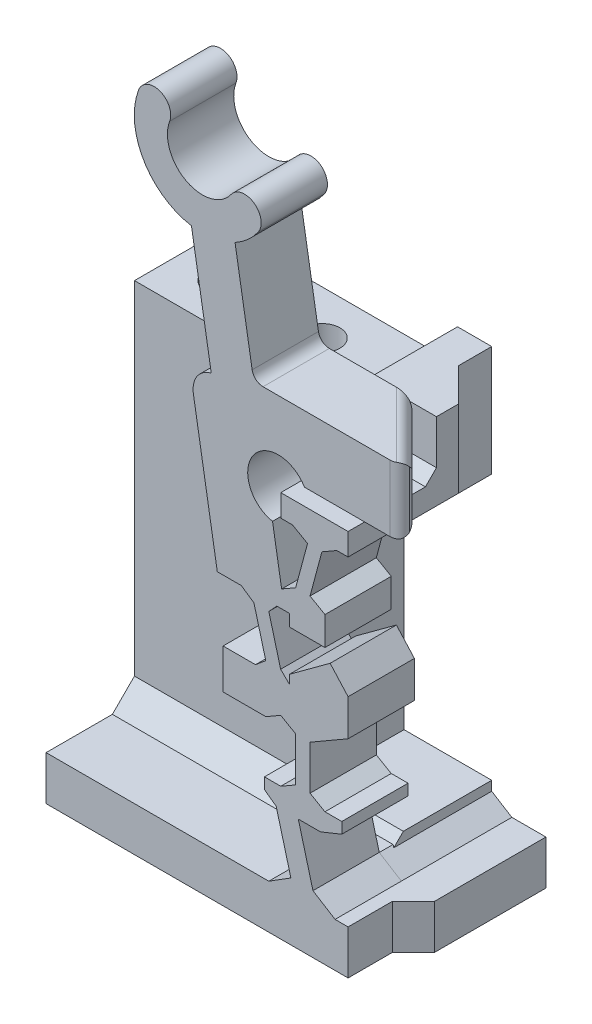
SolidWorks part; units mm, degrees
material "Nylon 6/12"
ref_plane "Front Plane" through (0, 0, 0) normal (0, 0, 1) x (1, 0, 0)
ref_plane "Top Plane" through (0, 0, 0) normal (0, 1, 0) x (1, 0, 0)
ref_plane "Right Plane" through (0, 0, 0) normal (1, 0, 0) x (0, 0, -1)
sketch "Sketch-SkeletonConfigUp" plane through (0, 0, 0) normal (0, 0, 1) x (1, 0, 0)
  line L0 (0, 0) -> (0, -50000) construction
  line L1 (0, 0) -> (4.5811, 6.2164) construction
  line L2 (9.8143, 13.3177) -> (4.5811, 13.945) construction
  line L3 (4.5811, 13.945) -> (2.9713, 10.4094) construction
  line L4 (2.9713, 10.4094) -> (4.5811, 6.2164) construction
  line L5 (4.5811, 13.945) -> (6.2429, 19.1409) construction
  line L6 (2.9713, 10.4094) -> (0.0405, 27.8193) construction
  line L7 (4.5811, 6.2164) -> (9.8143, 13.3177) construction
  line L8 (-587.3593, -797.0242) -> (9.8143, 13.3177) construction
  point P12 (0, 0)
  point P13 (0, 0)
  dimension "D2" = 7.7221
  dimension "D3" = 8.8212
  dimension "D4" = 5.2707
  dimension "D5" = 119.553
  dimension "D6" = 3.8848
  dimension "D7" = 5.4552
  dimension "D8" = 17.6549
  dimension "D9" = 4.4914
  dimension "D10" = 6.745
  dimension "D11" = 145.964
  dimension "D12" = 143.612
sketch "Sketch-SkeletonConfigDown" plane through (0, 0, 0) normal (0, 0, 1) x (1, 0, 0)
  line L0 (0, 0) -> (0, -50000) construction
  line L1 (0, 0) -> (4.5811, 6.2164) construction
  line L2 (9.8143, 13.3177) -> (4.5811, 13.945) construction
  line L3 (4.5811, 13.945) -> (6.1909, 10.4094) construction
  line L4 (6.1909, 10.4094) -> (4.5811, 6.2164) construction
  line L5 (4.5811, 13.945) -> (1.753, 18.6098) construction
  line L6 (6.1909, 10.4094) -> (-8.8652, 19.6294) construction
  line L7 (4.5811, 6.2164) -> (9.8143, 13.3177) construction
  line L8 (-589.9357, -800.5203) -> (9.8143, 13.3177) construction
  dimension "D2" = 7.7221
  dimension "D3" = 8.8212
  dimension "D4" = 5.2707
  dimension "D5" = 119.553
  dimension "D6" = 3.8848
  dimension "D7" = 5.4552
  dimension "D8" = 17.6549
  dimension "D9" = 4.4914
  dimension "D10" = 6.745
  dimension "D11" = 145.964
  dimension "D1" = 143.612
ref_plane "Plane-Cam Base" through (9.128, 0, 0) normal (1, 0, 0) x (0, 0, -1)
ref_plane "Plane-Down-to-Up Derailleur Clearance" through (6.628, 0, 0) normal (1, 0, 0) x (0, 0, -1)
ref_plane "Plane-Cam Cavity Roof" through (5.128, 0, 0) normal (1, 0, 0) x (0, 0, -1)
sketch "Sketch-SwitchBossUp" plane through (0, 0, 0) normal (0, 0, 1) x (1, 0, 0)
  line L0 (3.5811, 11.4759) -> (3.5811, 12.945) construction
  line L5 (5.5811, 12.5552) -> (5.5811, 11.263)
  line L7 (1.5115, 25.1048) -> (2.3566, 20.0847)
  line L8 (-0.4607, 24.7728) -> (0.4359, 19.4465)
  line L9 (2.9713, 10.4094) -> (0.0405, 27.8193) construction
  line L11 (-0.0396, 22.2712) -> (1.9326, 22.6032) construction
  line L15 (6.628, -23.7286) -> (6.628, 23.7286) construction
  line L16 (2.9713, 10.4094) -> (4.5811, 6.2164) construction
  line L17 (3.5811, 12.945) -> (3.5811, 14.945) construction
  line L18 (5.5811, 12.945) -> (5.5811, 14.945) construction
  line L19 (4.2561, 13.945) -> (4.9061, 13.945) construction
  line L20 (3.5811, 14.945) -> (5.5811, 14.945) construction
  line L21 (3.5811, 12.945) -> (5.5811, 12.945) construction
  line L22 (4.5811, 12.945) -> (4.5811, 14.945) construction
  line L23 (4.5811, 6.2164) -> (8.5405, 7.1023) construction
  line L24 (1.9713, 9.4094) -> (1.9713, 11.4094) construction
  line L25 (3.9713, 9.4094) -> (3.9713, 11.4094) construction
  line L26 (3.9713, 9.4094) -> (1.9713, 9.4094) construction
  line L27 (1.9713, 11.4094) -> (3.9713, 11.4094) construction
  line L28 (3.5811, 7.2164) -> (5.5811, 7.2164) construction
  line L29 (3.5811, 7.2164) -> (3.5811, 5.2164) construction
  line L30 (5.5811, 7.2164) -> (5.5811, 5.2164) construction
  line L31 (3.5811, 5.2164) -> (5.5811, 5.2164) construction
  line L32 (4.9061, 6.2164) -> (4.2561, 6.2164) construction
  line L40 (2.6348, 10.4094) -> (3.3077, 10.4094) construction
  line L66 (0.0405, 27.8193) -> (0.0405, 50027.8193) construction
  line L74 (0.7092, 11.7991) -> (-0.3728, 18.2264)
  line L75 (0.3841, 13.7302) -> (2.3564, 14.0622) construction
  line L76 (5.5811, 11.263) -> (5.5811, 12.5552) construction
  line L77 (5.5811, 7.6061) -> (6.628, 8.2105)
  line L80 (5.8152, 10.763) -> (6.628, 9.8603)
  line L81 (9.128, 1033.2419) -> (9.128, 20.0586) construction
  line L82 (4.6532, 17.0847) -> (9.028, 17.0847)
  line L85 (6.9307, 9.5241) -> (8.5405, 7.7363) construction
  line L88 (5.7256, 16.3347) -> (6.628, 16.3347)
  line L92 (3.7762, 8.3129) -> (6.9307, 9.5241) construction
  line L95 (2.3566, 20.0847) -> (7.4359, 20.0847)
  line L96 (7.4359, 20.0847) -> (9.028, 20.0847)
  line L97 (3.2085, 15.0241) -> (3.6203, 12.5779)
  line L98 (1.9713, 9.0197) -> (0.9713, 9.0197)
  line L99 (0.9713, 9.0197) -> (0.9713, 7.2164)
  line L100 (0.9713, 7.2164) -> (2.9061, 7.2164)
  line L101 (4.5811, 6.2164) -> (6.9307, 9.5241) construction
  line L103 (0.0405, 27.8193) -> (1.9448, 26.4638) construction
  line L104 (6.9307, 9.5241) -> (8.5405, 7.7363) construction
  line L107 (1.9713, 9.4094) -> (1.9713, 9.0197) construction
  line L109 (0.0405, 27.8193) -> (-2.1498, 28.6358) construction
  line L111 (6.628, 9.8603) -> (6.628, 8.2105)
  line L112 (6.628, 9.8603) -> (6.9307, 9.5241) construction
  line L113 (2.8424, 4.8267) -> (2.8424, 4.3267)
  line L114 (7.3693, 7.7363) -> (7.3563, 7.7363) construction
  line L121 (5.0383, -1.1653) -> (5.0383, 1.4614) construction
  line L122 (2.8616, 17.0847) -> (3.2085, 15.0241) construction
  line L127 (5.5811, 15.3347) -> (5.5811, 14.945) construction
  line L130 (6.0388, 0.837) -> (6.628, 0.837)
  line L132 (2.8424, 4.3267) -> (3.3749, 3.937)
  line L133 (2.9028, 9.4094) -> (2.4375, 9.0197)
  line L134 (4.5811, 10.4094) -> (4.5811, 13.945) construction
  line L135 (4.5811, 10.4094) -> (4.5811, 6.2164) construction
  line L137 (3.9713, 9.4094) -> (5.5811, 7.2164) construction
  line L139 (5.8152, 10.763) -> (3.9713, 9.4094)
  line L141 (4.0386, 1.4604) -> (3.0388, 0.8347)
  line L142 (3.0388, 0.8347) -> (3.0388, -1.1653)
  line L143 (9.128, 20.0586) -> (9.128, 18.3333) construction
  line L145 (9.128, 16.6071) -> (9.128, -49992.4167) construction
  line L147 (5.5811, 11.263) -> (5.5811, 12.5552) construction
  line L150 (3.0388, -1.1653) -> (5.0383, -1.1653)
  line L151 (3.3749, 3.937) -> (4.3749, 3.937) construction
  line L152 (4.792, 14.945) -> (4.2561, 12.945)
  line L153 (5.442, 14.945) -> (4.9061, 12.945)
  line L157 (3.5811, 16.3347) -> (3.5811, 15.3347)
  line L158 (6.117, 15.3347) -> (6.628, 15.3347)
  line L162 (3.0398, 11.4094) -> (3.5757, 9.4094)
  line L164 (2.3668, 11.4094) -> (2.9028, 9.4094)
  line L169 (4.2561, 7.2164) -> (4.2561, 5.2164)
  line L170 (4.9061, 5.2164) -> (4.9061, 7.2164)
  line L175 (4.2561, 7.2164) -> (3.5811, 7.6061)
  line L176 (4.9061, 7.2164) -> (5.5811, 7.6061)
  line L177 (5.5811, 7.2164) -> (5.5811, 7.6061) construction
  line L179 (4.2561, 5.2164) -> (3.5811, 4.8267)
  line L180 (3.5811, 5.2164) -> (3.5811, 4.8267) construction
  line L181 (3.5811, 4.8267) -> (2.8424, 4.8267)
  line L183 (4.9061, 5.2164) -> (5.5811, 4.8267)
  line L184 (5.5811, 5.2164) -> (5.5811, 4.8267) construction
  line L186 (9.128, -23.7286) -> (9.128, 23.7286) construction
  line L191 (3.9713, 11.4094) -> (3.9713, 11.7991) construction
  line L192 (3.9713, 11.7991) -> (3.9713, 11.263)
  line L193 (4.9061, 12.945) -> (5.5811, 12.5552)
  line L194 (4.2561, 12.945) -> (3.6203, 12.5779)
  line L195 (3.9713, 11.263) -> (5.5811, 11.263)
  line L196 (3.9713, 9.4094) -> (3.9713, 9.0197)
  line L197 (3.5811, 7.2164) -> (3.5811, 7.6061) construction
  line L199 (3.5811, 7.6061) -> (2.9061, 7.2164)
  line L201 (2.8424, 4.3267) -> (2.8424, 3.937) construction
  line L202 (2.8424, 3.937) -> (3.3749, 3.937) construction
  line L204 (5.0383, 1.437) -> (3.0388, 1.437) construction
  line L205 (3.0388, 1.437) -> (3.0388, 0.8347) construction
  line L206 (5.0383, 1.4614) -> (6.0388, 0.837)
  line L207 (9.128, 18.3333) -> (9.128, 16.6071) construction
  line L208 (6.628, -1.1653) -> (6.628, 0.837)
  line L209 (9.128, 20.0586) -> (9.128, 16.6071) construction
  line L211 (5.0383, 1.4614) -> (4.3749, 3.937)
  line L212 (4.0386, 1.4604) -> (3.3749, 3.937)
  line L214 (4.792, 14.945) -> (4.1169, 15.3347)
  line L215 (4.1169, 15.3347) -> (3.5811, 15.3347)
  line L216 (5.442, 14.945) -> (6.117, 15.3347)
  line L217 (5.5811, 12.945) -> (5.5811, 12.5552) construction
  line L218 (5.442, 14.945) -> (5.442, 15.3347) construction
  line L219 (6.117, 15.3347) -> (4.1169, 15.3347) construction
  line L221 (9.028, 17.0847) -> (9.028, 20.0847)
  line L224 (3.5811, 16.3347) -> (5.7256, 16.3347)
  line L232 (6.628, 15.3347) -> (6.628, 16.3347)
  line L233 (6.628, -1.1653) -> (5.0383, -1.1653)
  line L236 (2.4375, 9.0197) -> (1.9713, 9.0197)
  line L240 (4.3749, 3.937) -> (5.3749, 3.937)
  line L241 (5.3749, 3.937) -> (6.3424, 4.3267)
  line L248 (2.8616, 17.0847) -> (4.6532, 17.0847) construction
  line L249 (3.5757, 9.4094) -> (3.9713, 9.0197)
  line L250 (3.0398, 11.4094) -> (3.4039, 11.7991)
  line L251 (3.4039, 11.7991) -> (3.9713, 11.7991)
  line L252 (2.3668, 11.4094) -> (1.794, 11.7991)
  line L253 (1.794, 11.7991) -> (0.7092, 11.7991)
  line L254 (1.794, 11.7991) -> (3.4039, 11.7991) construction
  line L256 (2.4375, 9.0197) -> (3.9713, 9.0197) construction
  line L367 (5.5811, 4.8267) -> (6.3424, 4.8267)
  line L368 (6.3424, 4.8267) -> (6.3424, 4.3267)
  arc A0 (1.5115, 25.1048) -> (2.5558, 26.0289) centre (0.0405, 27.8193) ccw
  arc A1 (-0.4607, 24.7728) -> (-2.8525, 28.8978) centre (0.0405, 27.8193) cw
  arc A2 (-2.8525, 28.8978) -> (-1.447, 28.3738) centre (-2.1498, 28.6358) cw
  arc A3 (2.5558, 26.0289) -> (1.3338, 26.8987) centre (1.9448, 26.4638) ccw
  arc A4 (-1.447, 28.3738) -> (1.3338, 26.8987) centre (0.0405, 27.8193) ccw
  arc A5 (3.5811, 12.945) -> (3.5811, 14.945) centre (3.1778, 13.945) ccw construction
  arc A6 (5.5811, 12.945) -> (5.5811, 14.945) centre (5.9843, 13.945) cw construction
  arc A9 (3.5811, 7.2164) -> (3.5811, 5.2164) centre (3.1779, 6.2164) cw construction
  arc A10 (5.5811, 7.2164) -> (5.5811, 5.2164) centre (5.9844, 6.2164) ccw construction
  arc A19 (-0.3728, 18.2264) -> (0.4359, 19.4465) centre (0.6836, 18.4042) cw
  circle A28 centre (0.0405, 27.8193) radius 2.3375 construction
  arc A37 (3.2085, 15.0241) -> (4.6532, 17.0847) centre (3.4651, 16.381) cw
  point P53 (4.5811, 13.945)
  point P93 (0.9465, 22.4372)
  dimension "D23" = 1.5875
  dimension "D24" = 0.75
  dimension "D2" = 2
  dimension "D5" = 2
  dimension "D6" = 0.65
  dimension "D8" = 42
  dimension "D16" = 42
  dimension "D27" = 120
  dimension "D28" = 120
  dimension "D29" = 120
  dimension "D30" = 120
  dimension "D17" = 0.5
  dimension "D21" = 1
  dimension "D9" = 17.5
  dimension "D22" = 1
  dimension "D38" = 2
  dimension "D39" = 0.5
  dimension "D40" = 60
  dimension "D41" = 1
  dimension "D42" = 45
  dimension "D43" = 120
  dimension "D10" = 15
  dimension "D12" = 2.5
  dimension "D13" = 1
  dimension "D19" = 1
  dimension "D25" = 15
  dimension "D26" = 120
  dimension "D35" = 120
  dimension "D20" = 3
  dimension "D48" = 2
  dimension "D49" = 0.6
  dimension "D7" = 0.75
  dimension "D14" = 3
  dimension "D82" = 1
  dimension "D83" = 3.5
  dimension "D15" = 0.65
  dimension "D18" = 15
extrude "Boss-Switch Body" add sketch "Sketch-SwitchBossUp" along normal blind 3
sketch "Sketch1" plane through (0, 0, 0) normal (0, 0, -1) x (-1, 0, 0)
  line L1 (-7.5811, -1.1653) -> (0.4122, -1.1653)
  line L2 (-7.5811, -1.1653) -> (-7.5811, 0.837)
  line L4 (0.4122, -1.1653) -> (0.4122, 0.8347)
  line L5 (-3.5811, 18.8347) -> (-7.5811, 18.8347)
  line L10 (-7.5811, 18.8347) -> (-7.5811, 15.3347)
  line L11 (-4.0386, 1.4604) -> (-5.0386, 1.4604)
  line L12 (-7.5811, 15.3347) -> (-3.5811, 15.3347)
  line L13 (-4.0386, 1.4604) -> (-3.0388, 0.8347)
  line L14 (-3.5811, 15.3347) -> (-3.5811, 18.8347)
  line L20 (-4.3749, 3.937) -> (-5.0383, 1.4614) construction
  line L22 (-3.0388, -1.1653) -> (-6.628, -1.1653) construction
  line L23 (-3.0388, 0.8347) -> (0.4122, 0.8347)
  line L24 (-5.0386, 1.4604) -> (-6.0388, 0.837)
  line L25 (-6.0388, 0.837) -> (-7.5811, 0.837)
  dimension "D1" = 3.5
extrude "Boss-Flange Width" add sketch "Sketch1" along normal blind 5
ref_plane "Plane-Sta2Sit Groove" through (0.0405, 0, 0) normal (1, 0, 0) x (0, 0, -1)
ref_plane "Plane-Cam Outer Surface" through (-12.0395, 0, 0) normal (1, 0, 0) x (0, 0, -1)
ref_plane "Plane-FlangeTop" through (-7.0395, 0, 0) normal (1, 0, 0) x (0, 0, -1)
sketch "Sketch2" plane through (-7.0395, 0, 0) normal (1, 0, 0) x (0, 0, -1)
  line L0 (5, 15.3347) -> (-3, 15.3347) construction
  line L1 (5, 17.3347) -> (1, 17.3347)
  line L2 (5, 17.3347) -> (5, 15.3347)
  line L3 (5, 15.3347) -> (1, 15.3347)
  line L4 (1, 17.3347) -> (1, 15.3347)
  line L5 (-3, -1.1653) -> (-3, 0.837) construction
  line L11 (5, 0.8347) -> (-3, 0.8347)
  line L12 (5, 0.8347) -> (5, -1.1653)
  line L13 (5, -1.1653) -> (-3, -1.1653)
  line L14 (-3, 0.8347) -> (-3, -1.1653)
  line L15 (0, 10.4094) -> (0, 27.8193) construction
  line L17 (5, 0.837) -> (5, -1.1653) construction
  line L18 (-3, 0.8347) -> (0, 0.8347) construction
  dimension "D1" = 1
  dimension "D2" = 2
extrude "Boss-Flange Height" add sketch "Sketch2" along normal up to surface (11.6675 mm away)
sketch "Sketch24" plane through (0, 0, 0) normal (0, 0, 1) x (1, 0, 0)
  line L0 (3.5811, 16.3347) -> (7.5811, 16.3347)
  line L1 (7.5811, 17.0847) -> (7.5811, 15.3347) construction
  line L2 (3.5811, 16.3347) -> (3.5811, 18.8347)
  line L3 (3.5811, 18.8347) -> (7.5811, 18.8347)
  line L4 (7.5811, 18.8347) -> (7.5811, 16.3347)
extrude "Cut-Wall Clearance" cut sketch "Sketch24" against normal up to surface (1 mm away) up to face at (-1.7292, 16.3347, -1)
sketch "Sketch10" plane through (0, 15.3347, 0) normal (0, 1, 0) x (1, 0, 0)
  line L0 (9.128, -23.7286) -> (9.128, 23.7286) construction
  line L1 (7.5811, 5) -> (5.128, 5)
  line L2 (7.5811, 5) -> (7.5811, 2)
  line L3 (7.5811, 2) -> (5.128, 2)
  line L5 (4.628, 7) -> (4.628, 1) construction
  line L6 (3.5811, 1) -> (-7.0395, 1) construction
  line L8 (5.128, 5) -> (5.128, 2)
  dimension "D1" = 1
  dimension "D2" = 0.5
  dimension "D3" = 4.5
extrude "Cut-Up-To-Down Derailleur Clearance" cut sketch "Sketch10" along normal up to next
sketch "Sketch17" plane through (0, 15.3347, 0) normal (0, -1, 0) x (1, 0, 0)
  line L0 (5.128, -5) -> (-7.0395, -5)
  line L1 (5.128, -5) -> (-7.0395, -5) construction
  line L2 (-7.0395, -5) -> (-7.0395, -1)
  line L3 (-7.0395, -1) -> (5.128, -1)
  line L4 (5.128, -1) -> (5.128, -5)
  line L5 (-7.0395, -1) -> (-7.0395, -5) construction
extrude "Boss-Flange Support" add sketch "Sketch17" along normal up to surface (14.5 mm away) up to face at (-2.0003, 0.8347, -1)
sketch "Sketch-HolePositions" plane through (0, -1.1653, 0) normal (0, -1, 0) x (1, 0, 0)
  line L0 (-7.0395, -3) -> (7.5811, -3) construction
  line L1 (7.5811, -5) -> (-7.0395, -5) construction
  line L2 (7.5811, -5) -> (7.5811, 0) construction
  line L4 (-7.0395, -22.2167) -> (-7.0395, 22.2167) construction
  point P6 (-5.0395, -3)
  point P7 (-0.5395, -3)
  dimension "D1" = 2
  dimension "D2" = 4.5
  dimension "D3" = 2
sketch "Sketch6" plane through (0, -1.1653, 0) normal (0, -1, 0) x (-1, 0, 0)
  point P0 (5.0395, 3)
  point P3 (0.5395, 3)
hole_wizard "Tap Drill for M2x0.4 Tap1" positions "Sketch6" profile "Sketch5" hole size "M2x0.4" standard "ANSI Metric" end condition through all
sketch "Sketch5" plane through (-5.0395, -1.1653, -3) normal (1, 0, 0) x (0, 0, -1)
  line L0 (0, 0) -> (0, 30.5511)
  line L1 (0, 30.5511) -> (0.8, 30.5511)
  line L2 (0.8, 30.5511) -> (0.8, 0)
  line L5 (0.8, 0) -> (0, 0)
  line L11 (0, -6.35) -> (0, 107.95) construction
  dimension "Thru Hole Dia." = 1.6
  dimension "Thru Hole Depth" = 30.5511
sketch "Sketch9" plane through (0, -1.1653, 0) normal (0, -1, 0) x (1, 0, 0)
  point P0 (-5.0395, -3)
  point P3 (-0.5395, -3)
hole_wizard "M2 Clearance Hole2" positions "Sketch9" profile "Sketch8" hole size "M2" standard "ANSI Metric"
sketch "Sketch8" plane through (-5.0395, -1.1653, -3) normal (1, 0, 0) x (0, 0, -1)
  line L0 (0, 0) -> (0, 15.721)
  line L1 (0, 15.721) -> (1.2, 15)
  line L2 (1.2, 15) -> (1.2, 0)
  line L5 (1.2, 0) -> (0, 0)
  line L10 (0, 15.721) -> (-1.2, 15) construction
  line L11 (0, -6.35) -> (0, 107.95) construction
  dimension "Hole Dia." = 2.4
  dimension "Hole Depth" = 15
  dimension "Drill Angle" = 118
sketch "Sketch-Measurements for Derailleur Ramps" [suppressed] plane through (0, 0, 0) normal (0, 0, 1) x (1, 0, 0)
  line L0 (3.184, 15.1695) -> (2.4687, 19.4188)
  line L1 (2.8264, 17.2941) -> (1.8402, 17.1281)
  line L2 (2.9713, 10.4094) -> (0.0405, 27.8193) construction
  line L3 (1.8402, 17.1281) -> (-1.3081, 15.0016)
  line L4 (6.1909, 10.4094) -> (-8.8652, 19.6294) construction
  line L5 (1.8402, 17.1281) -> (2.6012, 12.6077)
  line L6 (2.6012, 12.6077) -> (-1.3081, 15.0016)
  line L7 (0.2661, 16.0649) -> (0.2661, 17.1281)
  line L8 (0.2661, 17.1281) -> (1.8402, 17.1281)
  line L9 (6.1909, 10.4094) -> (2.9713, 10.4094)
  line L10 (5.386, 8.3129) -> (3.7762, 8.3129)
  line L11 (2.6116, 18.5698) -> (1.5115, 25.1048) construction
  line L12 (6.1909, 10.4094) -> (4.5811, 6.2164) construction
  line L13 (4.5811, 8.3129) -> (4.5811, 8.7912)
  line L14 (4.5811, 6.2164) -> (5.386, 8.3129)
  line L15 (2.9713, 10.4094) -> (4.5811, 6.2164) construction
  line L16 (3.7762, 8.3129) -> (4.5811, 6.2164)
  line L17 (5.386, 8.3129) -> (5.386, 8.7912)
  dimension "D1" = 1.5742
  dimension "D2" = 0.8049
sketch "Sketch12" plane through (0, 20.0847, 0) normal (0, 1, 0) x (1, 0, 0)
  line L0 (6.528, 0) -> (9.028, -2.5)
  line L1 (9.028, -2.5) -> (9.028, 0)
  line L2 (9.028, 0) -> (6.528, 0)
  line L3 (9.028, -3) -> (9.028, 0) construction
  line L6 (9.028, 0) -> (2.3566, 0) construction
  dimension "D1" = 45
extrude "Cut-Up-to-Down Cantilever Slope" cut sketch "Sketch12" against normal up to next
ref_plane "Plane1" through (0, 7.1023, 0) normal (0, 1, 0) x (1, 0, 0)
ref_plane "Plane-Cantilever Cut" [suppressed] through (7.0848, 8.5204, -1.9058) normal (-0.6301, -0.7578, 0.1695) x (-0.7765, 0.6151, -0.1368)
sketch "Sketch14" [suppressed] plane through (7.0848, 8.5204, -1.9058) normal (-0.6301, -0.7578, 0.1695) x (-0.7765, 0.6151, -0.1368)
  line L0 (2.3023, -1.6911) -> (-0.3551, -1.6911)
  line L2 (2.3023, -4.3362) -> (2.3023, -1.6911)
  line L3 (-0.3551, -1.6911) -> (-0.3551, -4.4608)
  line L5 (-0.3551, -4.4608) -> (1.0087, -5.0843)
  line L6 (1.0087, -5.0843) -> (2.3023, -4.3362)
extrude "Cut-Down-to-Up Cantilever Slope" [suppressed] cut sketch "Sketch14" against normal up to next
ref_plane "Plane-Symmetry Plane" through (0, 0, 1.5) normal (0, 0, 1) x (1, 0, 0)
sketch "Sketch-Cable Center Point" plane through (0, 0, 1.5) normal (0, 0, 1) x (1, 0, 0)
  line L0 (0.0405, 27.8193) -> (0.1722, 27.0366)
  line L1 (2.9713, 10.4094) -> (0.0405, 27.8193) construction
  point P0 (0.0405, 27.8193)
  dimension "D1" = 0.7937
chamfer "Chamfer-Flange Support" distance 1.5 angle 45 1 edges at (3.5811, 17.3347, -3)
chamfer "Chamfer-Flange Support 2" distance 1.5 angle 45 2 edges at (5.128, 17.0847, -2) (5.128, 15.3347, -1.5)
chamfer "Chamfer-Flange Support 3" distance 1 angle 45 1 edges at (-2.0003, 0.8347, -1)
chamfer "Chamfer3" distance 0.5 angle 45 3 edges at (3.5811, 15.8347, -1) (5.1045, 15.3347, -1) (5.5811, 16.3347, -1)
chamfer "Chamfer7" [suppressed] distance 1 angle 45
sketch "Sketch23" plane through (0, 0, -1) normal (0, 0, 1) x (1, 0, 0)
  line L0 (5.128, 1.8347) -> (1.1605, 1.8347)
  line L1 (-7.0395, 1.8347) -> (5.128, 1.8347) construction
  line L2 (1.1605, 1.8347) -> (1.1605, 13.8347)
  line L3 (1.1605, 13.8347) -> (5.128, 13.8347)
  line L4 (5.128, 13.8347) -> (5.128, 1.8347)
  line L5 (0.6605, -1.1653) -> (0.6605, 13.8347) construction
  dimension "D1" = 0.5
extrude "Cut-Gap for Printing" cut sketch "Sketch23" against normal through all
sketch "Sketch25" plane through (0, 0, 0) normal (0, 0, 1) x (1, 0, 0)
  line L0 (6.628, 15.3347) -> (7.5811, 15.3347)
  line L1 (7.5811, 15.3347) -> (7.5811, 18.8347)
  line L2 (7.5811, 18.8347) -> (6.628, 18.8347)
  line L3 (6.628, -23.7286) -> (6.628, 23.7286) construction
  line L4 (7.5811, 18.8347) -> (3.5811, 18.8347) construction
  line L5 (6.628, 18.8347) -> (6.628, 15.3347)
extrude "Cut-Derailleur Clearance" cut sketch "Sketch25" against normal through all
chamfer "Chamfer8" distance 1 angle 45 1 edges at (6.628, -0.1641, 0)
fillet "Fillet1" radius 0.5 5 edges at (6.528, 18.5847, 0) (9.028, 18.5847, 3) (7.778, 20.0847, 1.25) (9.028, 18.5847, 2.5) (7.778, 17.0847, 1.25)
fillet "Fillet2" radius 0.5 1 edges at (2.3566, 20.0847, 1.5)
equation "\"axle-diameter\"=2"
equation "\"switch-thickness\"=12"
equation "\"base-width\"=4.0"
equation "\"axle-bushing-radius\"=3"
equation "\"clearance\"= 0.25"
equation "\"arm-width\"=1.5"
equation "\"min-diameter\"=70"
equation "\"alpha\"=143.6120"
equation "\"gamma\"=119.5526"
equation "\"delta\"=145.9637"
equation "\"epsilon\"=6.7452"
equation "\"l_AB\"=8.8212"
equation "\"l_AC\"=4.4914"
equation "\"l_BD\"=5.2707"
equation "\"l_CD\"=3.8848"
equation "\"l_CE\"=17.6549"
equation "\"l_DF\"=5.4552"
equation "\"l_OA\"=7.7221"
equation "\"D2@Sketch-SkeletonConfigUp\" = \"l_OA\""
equation "\"D3@Sketch-SkeletonConfigUp\" = \"l_AB\""
equation "\"D4@Sketch-SkeletonConfigUp\" = \"l_BD\""
equation "\"D5@Sketch-SkeletonConfigUp\" = \"gamma\""
equation "\"D6@Sketch-SkeletonConfigUp\" = \"l_CD\""
equation "\"D7@Sketch-SkeletonConfigUp\" = \"l_DF\""
equation "\"D8@Sketch-SkeletonConfigUp\" = \"l_CE\""
equation "\"D9@Sketch-SkeletonConfigUp\" = \"l_AC\""
equation "\"D_groove\"=3.175"
equation "\"D7@Sketch-SkeletonConfigDown\" = \"l_DF\""
equation "\"D6@Sketch-SkeletonConfigDown\" = \"l_CD\""
equation "\"D2@Sketch-SkeletonConfigDown\" = \"l_OA\""
equation "\"D3@Sketch-SkeletonConfigDown\" = \"l_AB\""
equation "\"D9@Sketch-SkeletonConfigDown\" = \"l_AC\""
equation "\"D8@Sketch-SkeletonConfigDown\" = \"l_CE\""
equation "\"D5@Sketch-SkeletonConfigDown\" = \"gamma\""
equation "\"D4@Sketch-SkeletonConfigDown\" = \"l_BD\""
equation "\"D1@Sketch-SkeletonConfigDown\" = \"alpha\""
equation "\"hinge_length\"=1.5"
equation "\"hinge_depth\"=0.25"
equation "\"D10@Sketch-SkeletonConfigUp\"=\"epsilon\""
equation "\"D11@Sketch-SkeletonConfigUp\"=\"delta\""
equation "\"D12@Sketch-SkeletonConfigUp\"=\"alpha\""
equation "\"D11@Sketch-SkeletonConfigDown\"=\"delta\""
equation "\"D10@Sketch-SkeletonConfigDown\"=\"epsilon\""
equation "\"EE_dx\"=8.9056"
equation "\"EE_dy\"=8.1898"
equation "\"r_groove\"=\"D_groove\"/2"
equation "\"t_wall\"=25.4/16"
equation "\"width_lower\"=\"D_groove\"+\"t_wall\""
equation "\"cable_to_bottom\"=30.6257"
equation "\"switch_EE-up_base_dy\"=24"
equation "\"switch_EE-down_base_dy\"=16"
equation "\"D_axle\"=25.4/8"
equation "\"D_up_to_down\"=16"
equation "\"D_down_to_up\"=25"
equation "\"t_cam_base\"=7.5"
equation "\"D23@Sketch-SwitchBossUp\"=\"D_groove\"/2"
equation "\"D1@Sketch-Cable Center Point\"=\"D_groove\"/4"
